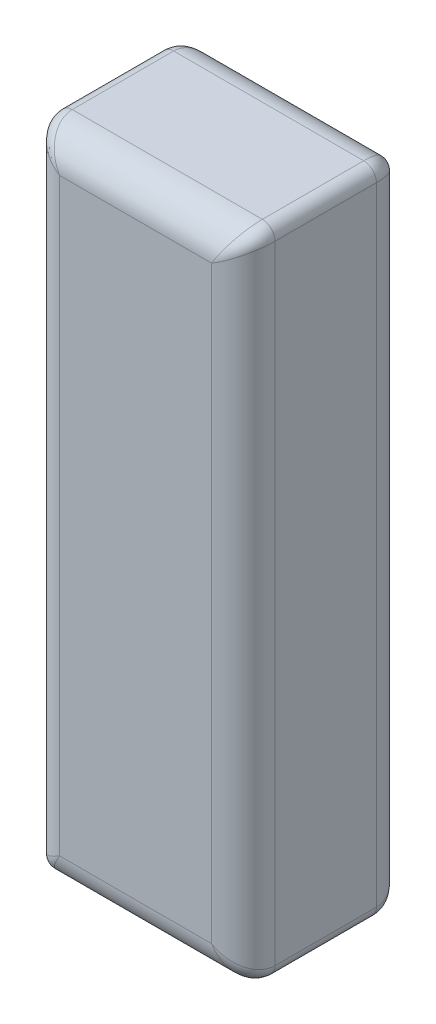
SolidWorks part; units mm, degrees
ref_plane "Plan de face" through (0, 0, 0) normal (0, 0, 1) x (1, 0, 0)
ref_plane "Plan de dessus" through (0, 0, 0) normal (0, 1, 0) x (1, 0, 0)
ref_plane "Plan de droite" through (0, 0, 0) normal (1, 0, 0) x (0, 0, -1)
sketch "Esquisse1" plane through (0, 0, 0) normal (0, 0, 1) x (1, 0, 0)
  line L1 (0, 0) -> (34, 0)
  line L2 (0, 0) -> (0, 103)
  line L3 (0, 103) -> (34, 103)
  line L4 (34, 0) -> (34, 103)
  dimension "D1" = 103
  dimension "D2" = 34
extrude "Boss.-Extru.1" add sketch "Esquisse1" along normal blind 26
fillet "Congé1" radius 5 8 edges at (0, 51.5, 0) (0, 51.5, 26) (34, 51.5, 0) (34, 51.5, 26) (17, 0, 0) (17, 0, 26) (17, 103, 0) (17, 103, 26)
fillet "Congé2" radius 2 12 edges at (1.4645, 101.5355, 24.5355) (1.4645, 101.5355, 1.4645) (32.5355, 101.5355, 24.5355) (32.5355, 101.5355, 1.4645) (1.4645, 1.4645, 24.5355) (1.4645, 1.4645, 1.4645) (32.5355, 1.4645, 24.5355) (32.5355, 1.4645, 1.4645) (0, 103, 13) (34, 103, 13) (0, 0, 13) (34, 0, 13)
